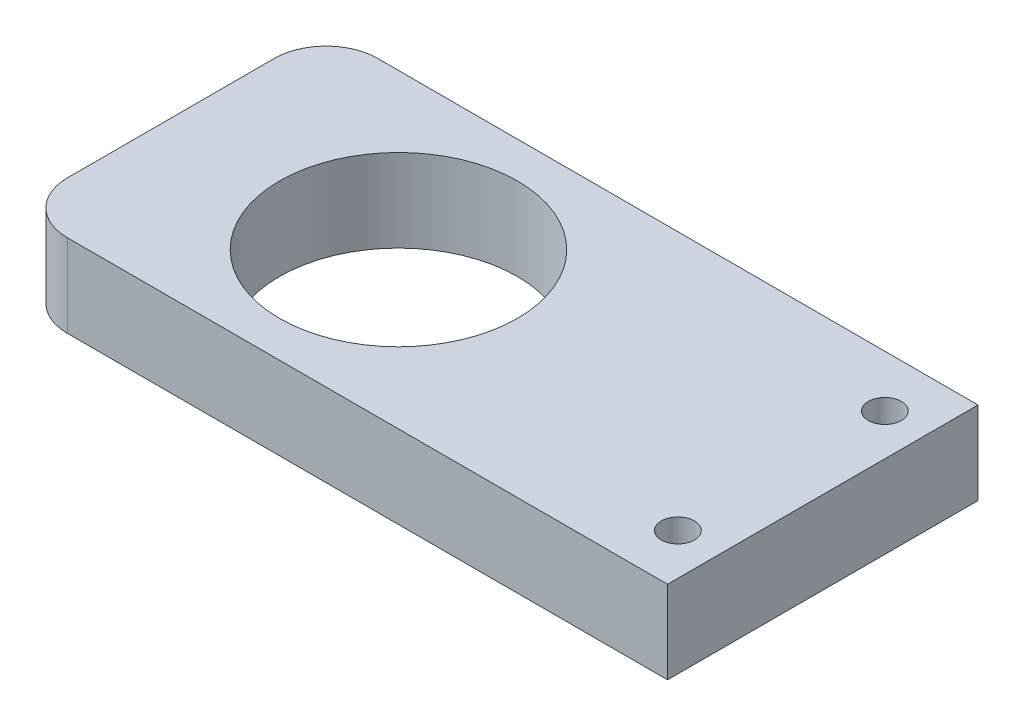
SolidWorks part; units mm, degrees
ref_plane "Front Plane" through (0, 0, 0) normal (0, 0, 1) x (1, 0, 0)
ref_plane "Top Plane" through (0, 0, 0) normal (0, 1, 0) x (1, 0, 0)
ref_plane "Right Plane" through (0, 0, 0) normal (1, 0, 0) x (0, 0, -1)
sketch "Sketch1" plane through (0, 0, 0) normal (0, 1, 0) x (1, 0, 0)
  line L1 (0, 0) -> (63, 0)
  line L2 (0, 0) -> (0, 30)
  line L3 (0, 30) -> (63, 30)
  line L4 (63, 0) -> (63, 30)
  circle A0 centre (22, 15) radius 11.5
  point P7 (0, 15)
  point P8 (0, 0)
  dimension "D3" = 23
  dimension "D4" = 22
  dimension "D1" = 63
  dimension "D2" = 30
extrude "Boss-Extrude1" add sketch "Sketch1" along normal blind 8
sketch "Sketch2" plane through (0, 8, 0) normal (0, 1, 0) x (1, 0, 0)
  line L0 (63, 0) -> (63, 30) construction
  line L1 (0, 0) -> (63, 0) construction
  line L2 (63, 30) -> (0, 30) construction
  circle A0 centre (59, 25) radius 1.6
  circle A1 centre (59, 5) radius 1.6
  point P4 (0, 0)
  dimension "D1" = 3.2
  dimension "D4" = 5
  dimension "D2" = 4
  dimension "D3" = 5
extrude "Cut-Extrude1" cut sketch "Sketch2" against normal through all
fillet "Fillet1" radius 5 2 edges at (0, 4, 0) (0, 4, -30)
